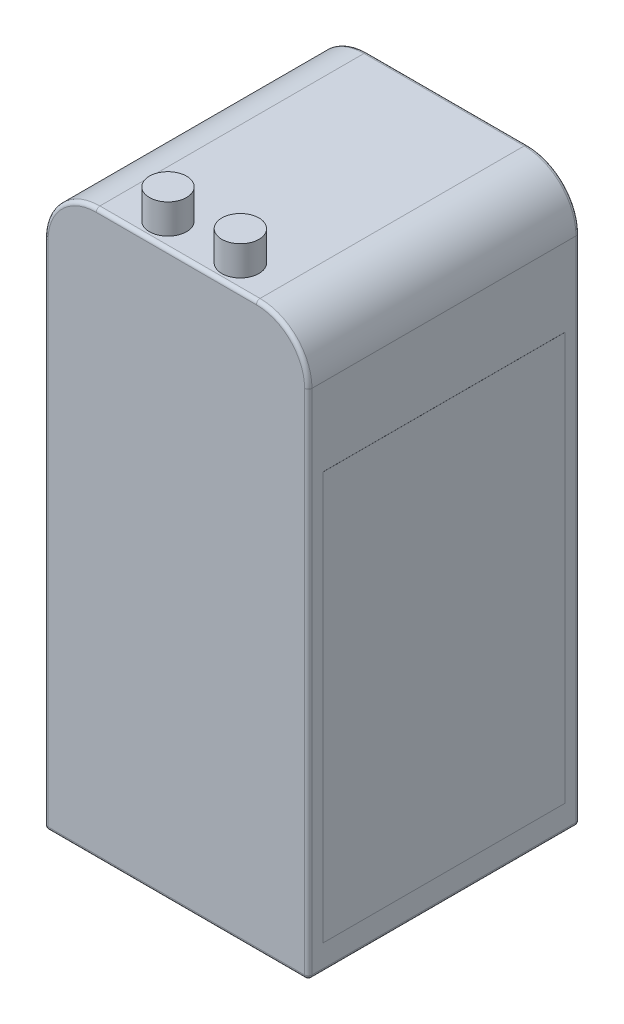
SolidWorks part; units mm, degrees
ref_plane "Front Plane" through (0, 0, 0) normal (0, 0, 1) x (1, 0, 0)
ref_plane "Top Plane" through (0, 0, 0) normal (0, 1, 0) x (1, 0, 0)
ref_plane "Right Plane" through (0, 0, 0) normal (1, 0, 0) x (0, 0, -1)
sketch "Sketch1" plane through (0, 0, 0) normal (0, 1, 0) x (1, 0, 0)
  line L1 (0, 0) -> (35.6, 0)
  line L2 (0, 0) -> (0, 36.6)
  line L3 (0, 36.6) -> (35.6, 36.6)
  line L4 (35.6, 0) -> (35.6, 36.6)
  dimension "D1" = 35.6
  dimension "D2" = 36.6
extrude "Boss-Extrude1" add sketch "Sketch1" along normal blind 76
sketch "Sketch2" plane through (0, 76, 0) normal (0, 1, 0) x (1, 0, 0)
  circle A0 centre (13.3548, 3.3233) radius 2.5
  circle A1 centre (23.1207, 3.3233) radius 2.5
  point P4 (13.3548, 3.3233)
  point P5 (23.1207, 3.3233)
  dimension "D1" = 5
  dimension "D2" = 5
extrude "Boss-Extrude2" add sketch "Sketch2" along normal blind 4 separate body
fillet "Fillet1" radius 7 2 edges at (0, 76, -18.3) (35.6, 76, -18.3)
fillet "Fillet2" radius 0.5 14 edges at (33.5497, 73.9497, 0) (35.6, 34.5, 0) (17.8, 0, 0) (0, 34.5, 0) (2.0503, 73.9497, 0) (17.8, 76, 0) (17.8, 0, -36.6) (35.6, 34.5, -36.6) (33.5497, 73.9497, -36.6) (17.8, 76, -36.6) (2.0503, 73.9497, -36.6) (0, 34.5, -36.6) (0, 0, -18.3) (35.6, 0, -18.3)
sketch "Sketch3" plane through (35.6, 0, 0) normal (1, 0, 0) x (0, 0, -1)
  line L0 (36.1, 0.5) -> (36.1, 69) construction
  line L1 (2, 58.5) -> (34.6, 58.5)
  line L2 (2, 58.5) -> (2, 3.5)
  line L3 (2, 3.5) -> (34.6, 3.5)
  line L4 (34.6, 58.5) -> (34.6, 3.5)
  line L5 (0.5, 69) -> (0.5, 0.5) construction
  line L6 (0.5, 0.5) -> (36.1, 0.5) construction
  dimension "D1" = 1.5
  dimension "D2" = 1.5
  dimension "D3" = 3
  dimension "D4" = 55
extrude "Boss-Extrude3" add sketch "Sketch3" along normal blind 0.01
